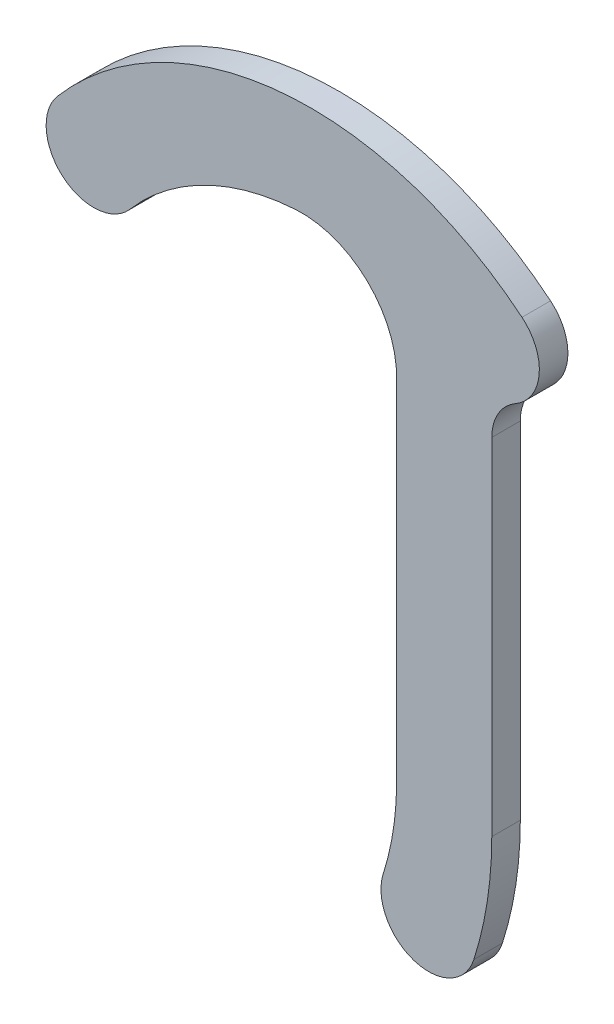
SolidWorks part; units mm, degrees
ref_plane "Plan de face" through (0, 0, 0) normal (0, 0, 1) x (1, 0, 0)
ref_plane "Plan de dessus" through (0, 0, 0) normal (0, 1, 0) x (1, 0, 0)
ref_plane "Plan de droite" through (0, 0, 0) normal (1, 0, 0) x (0, 0, -1)
sketch "Esquisse1" plane through (0, 0, 0) normal (0, 0, 1) x (1, 0, 0)
  line L0 (-10, -45) -> (-10, -8.6603)
  line L2 (0, -8.6603) -> (0, -45)
  arc A0 (0, -45) -> (-1.8801, -57.1192) centre (-40, -45) cw
  arc A1 (-1.8801, -57.1192) -> (-11.4101, -54.0894) centre (-6.6451, -55.6043) cw
  arc A2 (-10, -45) -> (-11.4101, -54.0894) centre (-40, -45) cw
  arc A3 (-2.5, 4.3301) -> (2.5, -4.3301) centre (0, 0) cw
  arc A4 (-2.5, 4.3301) -> (-10, -8.6603) centre (5, -8.6603) ccw
  arc A5 (2.5, -4.3301) -> (0, -8.6603) centre (5, -8.6603) ccw
  dimension "D3" = 40
  dimension "D2" = 5
  dimension "D4" = 45
  dimension "D5" = 56
extrude "Boss.-Extru.1" add sketch "Esquisse1" along normal mid plane 3
sketch "Esquisse4" plane through (0, 0, 1.5) normal (0, 0, 1) x (1, 0, 0)
  line L0 (0, 0) -> (-41.8402, -3.6605) construction
  line L1 (0, 0) -> (0, -17.0518) construction
  arc A0 (-38.0423, -6.9126) -> (-45.6381, -0.4085) centre (-41.8402, -3.6605) cw
  arc A1 (-38.0423, -6.9126) -> (-3.1755, -3.8622) centre (-19.0528, -23.173) cw
  arc A2 (-3.1755, -3.8622) -> (3.1755, 3.8622) centre (0, 0) ccw
  arc A3 (3.1755, 3.8622) -> (-45.6381, -0.4085) centre (-19.0528, -23.173) ccw
  dimension "D1" = 5
  dimension "D3" = 25
  dimension "D2" = 42
  dimension "D4" = 85
extrude "Boss.-Extru.2" add sketch "Esquisse4" against normal up to surface (3 mm away) up to face at (-3.9972, -27.4477, -1.5)
sketch "Esquisse2" plane through (0, 0, -1.5) normal (0, 0, -1) x (-1, 0, 0)
  circle A0 centre (0, 0) radius 2.5
  dimension "D1" = 5
extrude "Enlèv. mat.-Extru.3" cut sketch "Esquisse2" against normal blind 2
fillet "Congé1" radius 10 1 edges at (-7.8042, -0.8466, 0)
